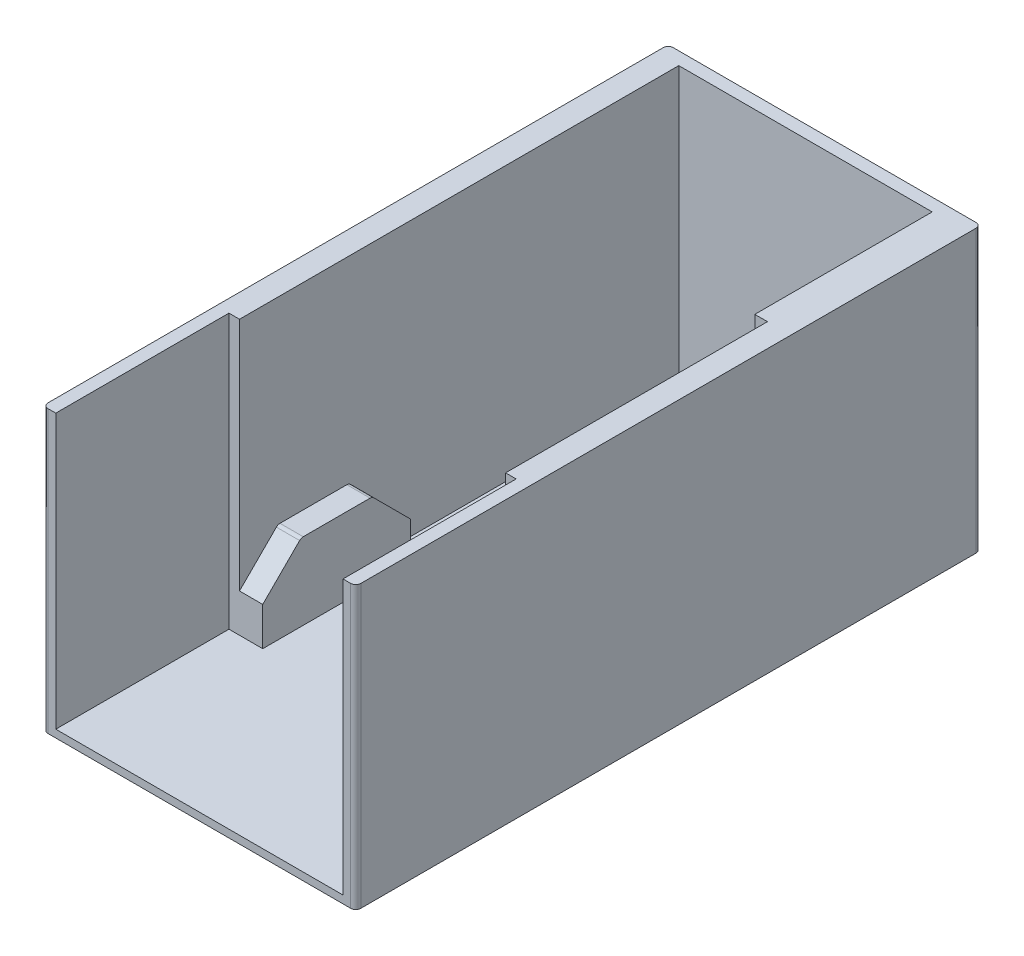
SolidWorks part; units mm, degrees
ref_plane "Front Plane" through (0, 0, 0) normal (0, 0, 1) x (1, 0, 0)
ref_plane "Top Plane" through (0, 0, 0) normal (0, 1, 0) x (1, 0, 0)
ref_plane "Right Plane" through (0, 0, 0) normal (1, 0, 0) x (0, 0, -1)
sketch "Sketch1" plane through (0, 0, 0) normal (0, 1, 0) x (1, 0, 0)
  line L0 (0, 0) -> (0, 2095.5) construction
  line L1 (-863.6, -520.7) -> (863.6, -520.7)
  line L2 (-863.6, -520.7) -> (-863.6, 520.7)
  line L3 (-863.6, 520.7) -> (863.6, 520.7)
  line L4 (863.6, -520.7) -> (863.6, 520.7)
  line L5 (-863.6, -520.7) -> (863.6, 520.7) construction
  line L6 (-863.6, 520.7) -> (863.6, -520.7) construction
  line L7 (-660.4, 520.7) -> (660.4, 520.7)
  line L8 (-660.4, 520.7) -> (-660.4, 1409.7)
  line L9 (-660.4, 1409.7) -> (660.4, 1409.7)
  line L10 (660.4, 520.7) -> (660.4, 1409.7)
  line L12 (-800.1, 1409.7) -> (800.1, 1409.7)
  line L13 (-800.1, 1409.7) -> (-800.1, 2095.5)
  line L14 (-800.1, 2095.5) -> (800.1, 2095.5)
  line L15 (800.1, 1409.7) -> (800.1, 2095.5)
  line L16 (-800.1, 2095.5) -> (723.9, 2095.5)
  line L17 (-800.1, 2095.5) -> (-800.1, 3162.3)
  line L18 (-800.1, 3162.3) -> (723.9, 3162.3)
  line L19 (723.9, 2095.5) -> (723.9, 3162.3)
  point P0 (0, 0)
  point P10 (0, 1409.7)
  point P13 (0, 2095.5)
  dimension "D1" = 1727.2
  dimension "D2" = 1041.4
  dimension "D3" = 1320.8
  dimension "D4" = 889
  dimension "D5" = 1600.2
  dimension "D6" = 685.8
  dimension "D7" = 1524
  dimension "D8" = 1066.8
sketch "Sketch2" plane through (0, 0, 0) normal (0, 1, 0) x (1, 0, 0)
  line L0 (-275, 3062.3) -> (-275, 3012.3) construction
  line L1 (-450, 3012.3) -> (-100, 3012.3)
  line L2 (-450, 3012.3) -> (-450, 2512.3)
  line L3 (-450, 2512.3) -> (-100, 2512.3)
  line L4 (-100, 3012.3) -> (-100, 2512.3)
  line L5 (-500, 3062.3) -> (-50, 3062.3)
  line L6 (-500, 3062.3) -> (-500, 2462.3)
  line L7 (-500, 2462.3) -> (-50, 2462.3)
  line L8 (-50, 3062.3) -> (-50, 2462.3)
  line L9 (-450, 2762.3) -> (-500, 2762.3) construction
  line L10 (100, 3012.3) -> (100, 2512.3)
  line L11 (100, 3012.3) -> (450, 3012.3)
  line L12 (450, 3012.3) -> (450, 2512.3)
  line L13 (100, 2512.3) -> (450, 2512.3)
  line L14 (50, 3062.3) -> (50, 2462.3)
  line L15 (50, 3062.3) -> (500, 3062.3)
  line L16 (500, 3062.3) -> (500, 2462.3)
  line L17 (50, 2462.3) -> (500, 2462.3)
  line L18 (100, 2312.3) -> (100, 1812.3)
  line L19 (100, 2312.3) -> (450, 2312.3)
  line L20 (450, 2312.3) -> (450, 1812.3)
  line L21 (100, 1812.3) -> (450, 1812.3)
  line L22 (50, 2362.3) -> (50, 1762.3)
  line L23 (50, 2362.3) -> (500, 2362.3)
  line L24 (500, 2362.3) -> (500, 1762.3)
  line L25 (50, 1762.3) -> (500, 1762.3)
  line L26 (100, 1612.3) -> (100, 1112.3)
  line L27 (100, 1612.3) -> (450, 1612.3)
  line L28 (450, 1612.3) -> (450, 1112.3)
  line L29 (100, 1112.3) -> (450, 1112.3)
  line L30 (50, 1662.3) -> (50, 1062.3)
  line L31 (50, 1662.3) -> (500, 1662.3)
  line L32 (500, 1662.3) -> (500, 1062.3)
  line L33 (50, 1062.3) -> (500, 1062.3)
  line L34 (100, 912.3) -> (100, 412.3)
  line L35 (100, 912.3) -> (450, 912.3)
  line L36 (450, 912.3) -> (450, 412.3)
  line L37 (100, 412.3) -> (450, 412.3)
  line L38 (50, 962.3) -> (50, 362.3)
  line L39 (50, 962.3) -> (500, 962.3)
  line L40 (500, 962.3) -> (500, 362.3)
  line L41 (50, 362.3) -> (500, 362.3)
  line L42 (-450, 2312.3) -> (-450, 1812.3)
  line L43 (-450, 2312.3) -> (-100, 2312.3)
  line L44 (-100, 2312.3) -> (-100, 1812.3)
  line L45 (-450, 1812.3) -> (-100, 1812.3)
  line L46 (-500, 2362.3) -> (-500, 1762.3)
  line L47 (-500, 2362.3) -> (-50, 2362.3)
  line L48 (-50, 2362.3) -> (-50, 1762.3)
  line L49 (-500, 1762.3) -> (-50, 1762.3)
  line L50 (-450, 1612.3) -> (-450, 1112.3)
  line L51 (-450, 1612.3) -> (-100, 1612.3)
  line L52 (-100, 1612.3) -> (-100, 1112.3)
  line L53 (-450, 1112.3) -> (-100, 1112.3)
  line L54 (-500, 1662.3) -> (-500, 1062.3)
  line L55 (-500, 1662.3) -> (-50, 1662.3)
  line L56 (-50, 1662.3) -> (-50, 1062.3)
  line L57 (-500, 1062.3) -> (-50, 1062.3)
  line L58 (-450, 912.3) -> (-450, 412.3)
  line L59 (-450, 912.3) -> (-100, 912.3)
  line L60 (-100, 912.3) -> (-100, 412.3)
  line L61 (-450, 412.3) -> (-100, 412.3)
  line L62 (-500, 962.3) -> (-500, 362.3)
  line L63 (-500, 962.3) -> (-50, 962.3)
  line L64 (-50, 962.3) -> (-50, 362.3)
  line L65 (-500, 362.3) -> (-50, 362.3)
  line L66 (-450, 3012.3) -> (100, 3012.3) construction
  line L67 (-450, 3012.3) -> (-450, 2312.3) construction
  line L68 (-50, 3062.3) -> (50, 3062.3) construction
  line L69 (0, 3062.3) -> (0, 2095.5) construction
  line L70 (-500, 2462.3) -> (-500, 2362.3)
  line L71 (-550, 3112.3) -> (550, 3112.3)
  line L72 (-550, 3112.3) -> (-550, 312.3)
  line L73 (-550, 312.3) -> (550, 312.3)
  line L74 (550, 3112.3) -> (550, 312.3)
  line L75 (-800.1, 3162.3) -> (723.9, 3162.3) construction
  dimension "D1" = 350
  dimension "D2" = 500
  dimension "D3" = 450
  dimension "D4" = 600
  dimension "D5" = 2
  dimension "D7" = 90
  dimension "D8" = 550
  dimension "D9" = 50
  dimension "D10" = 50
  dimension "D11" = 50
  dimension "D12" = 50
  dimension "D13" = 100
  dimension "D14" = 50
  dimension "D6" = 4
sketch "Resized Everything" plane through (0, 0, 0) normal (0, 1, 0) x (1, 0, 0)
  line L85 (-790.321, 2977.388) -> (-697.865, 2977.388)
  line L86 (-697.865, 2977.388) -> (-697.865, 3039.618)
  line L87 (-790.321, 3039.618) -> (-697.865, 3039.618)
  line L88 (-790.321, 2977.388) -> (-790.321, 3039.618)
  line L89 (-804.545, 2904.49) -> (-683.641, 2904.49)
  line L90 (-683.641, 2904.49) -> (-683.641, 2977.388)
  line L91 (-804.545, 2977.388) -> (-683.641, 2977.388)
  line L92 (-804.545, 2904.49) -> (-804.545, 2977.388)
  line L93 (-800.1, 3039.618) -> (-800.1, 3087.624)
  line L94 (-800.1, 3039.618) -> (-688.086, 3039.618)
  line L95 (-688.086, 3039.618) -> (-688.086, 3087.624)
  line L96 (-800.1, 3087.624) -> (-688.086, 3087.624)
  line L97 (-800.1, 3087.624) -> (-693.42, 3087.624)
  line L98 (-693.42, 3087.624) -> (-693.42, 3162.3)
  line L99 (-800.1, 3162.3) -> (-693.42, 3162.3)
  line L100 (-800.1, 3087.624) -> (-800.1, 3162.3)
  line L101 (-779.093, 3113.3) -> (-779.093, 3106.3)
  line L102 (-779.093, 3113.3) -> (-747.593, 3113.3)
  line L103 (-747.593, 3155.3) -> (-747.593, 3113.3)
  line L104 (-779.093, 3155.3) -> (-747.593, 3155.3)
  line L105 (-779.093, 3155.3) -> (-779.093, 3113.3)
  line L106 (-775.593, 3151.8) -> (-751.093, 3151.8)
  line L107 (-751.093, 3151.8) -> (-751.093, 3116.8)
  line L108 (-775.593, 3116.8) -> (-751.093, 3116.8)
  line L109 (-775.593, 3151.8) -> (-775.593, 3116.8)
  line L110 (-740.593, 3106.3) -> (-740.593, 3064.3)
  line L111 (-740.593, 3064.3) -> (-709.093, 3064.3)
  line L112 (-709.093, 3106.3) -> (-709.093, 3064.3)
  line L113 (-740.593, 3106.3) -> (-709.093, 3106.3)
  line L114 (-737.093, 3102.8) -> (-737.093, 3067.8)
  line L115 (-737.093, 3067.8) -> (-712.593, 3067.8)
  line L116 (-712.593, 3102.8) -> (-712.593, 3067.8)
  line L117 (-737.093, 3102.8) -> (-712.593, 3102.8)
  line L118 (-740.593, 3155.3) -> (-740.593, 3113.3)
  line L119 (-740.593, 3113.3) -> (-709.093, 3113.3)
  line L120 (-709.093, 3155.3) -> (-709.093, 3113.3)
  line L121 (-740.593, 3155.3) -> (-709.093, 3155.3)
  line L122 (-737.093, 3151.8) -> (-737.093, 3116.8)
  line L123 (-737.093, 3151.8) -> (-712.593, 3151.8)
  line L124 (-712.593, 3151.8) -> (-712.593, 3116.8)
  line L125 (-737.093, 3116.8) -> (-712.593, 3116.8)
  line L126 (-740.593, 3008.3) -> (-740.593, 2966.3)
  line L127 (-740.593, 2966.3) -> (-709.093, 2966.3)
  line L128 (-709.093, 3008.3) -> (-709.093, 2966.3)
  line L129 (-740.593, 3008.3) -> (-709.093, 3008.3)
  line L130 (-737.093, 3004.8) -> (-737.093, 2969.8)
  line L131 (-737.093, 2969.8) -> (-712.593, 2969.8)
  line L132 (-712.593, 3004.8) -> (-712.593, 2969.8)
  line L133 (-737.093, 3004.8) -> (-712.593, 3004.8)
  line L134 (-740.593, 3057.3) -> (-740.593, 3015.3)
  line L135 (-740.593, 3015.3) -> (-709.093, 3015.3)
  line L136 (-709.093, 3057.3) -> (-709.093, 3015.3)
  line L137 (-740.593, 3057.3) -> (-709.093, 3057.3)
  line L138 (-737.093, 3053.8) -> (-737.093, 3018.8)
  line L139 (-737.093, 3053.8) -> (-712.593, 3053.8)
  line L140 (-712.593, 3053.8) -> (-712.593, 3018.8)
  line L141 (-737.093, 3018.8) -> (-712.593, 3018.8)
  line L142 (-779.093, 3057.3) -> (-779.093, 3015.3)
  line L143 (-779.093, 3015.3) -> (-747.593, 3015.3)
  line L144 (-747.593, 3057.3) -> (-747.593, 3015.3)
  line L145 (-779.093, 3057.3) -> (-747.593, 3057.3)
  line L146 (-775.593, 3053.8) -> (-775.593, 3018.8)
  line L147 (-775.593, 3018.8) -> (-751.093, 3018.8)
  line L148 (-751.093, 3053.8) -> (-751.093, 3018.8)
  line L149 (-775.593, 3053.8) -> (-751.093, 3053.8)
  line L150 (-779.093, 3106.3) -> (-779.093, 3064.3)
  line L151 (-779.093, 3064.3) -> (-747.593, 3064.3)
  line L152 (-747.593, 3106.3) -> (-747.593, 3064.3)
  line L153 (-779.093, 3106.3) -> (-747.593, 3106.3)
  line L154 (-775.593, 3102.8) -> (-775.593, 3067.8)
  line L155 (-775.593, 3102.8) -> (-751.093, 3102.8)
  line L156 (-751.093, 3102.8) -> (-751.093, 3067.8)
  line L157 (-775.593, 3067.8) -> (-751.093, 3067.8)
  line L158 (-782.593, 3158.8) -> (-705.593, 3158.8)
  line L159 (-705.593, 3158.8) -> (-705.593, 2962.8)
  line L160 (-782.593, 2962.8) -> (-705.593, 2962.8)
  line L161 (-782.593, 3158.8) -> (-782.593, 2962.8)
  line L162 (-779.093, 3008.3) -> (-779.093, 2966.3)
  line L163 (-779.093, 2966.3) -> (-747.593, 2966.3)
  line L164 (-747.593, 3008.3) -> (-747.593, 2966.3)
  line L165 (-779.093, 3008.3) -> (-747.593, 3008.3)
  line L166 (-775.593, 3004.8) -> (-775.593, 2969.8)
  line L167 (-775.593, 3004.8) -> (-751.093, 3004.8)
  line L168 (-751.093, 3004.8) -> (-751.093, 2969.8)
  line L169 (-775.593, 2969.8) -> (-751.093, 2969.8)
sketch "Sketch6" plane through (0, 0, 0) normal (0, 1, 0) x (1, 0, 0)
  line L0 (-800.1, 3162.3) -> (723.9, 3162.3) construction
  line L1 (-748.0935, 2917.905) -> (-748.0935, 3167.3) construction
  line L2 (-809.2275, 2917.905) -> (-686.9595, 2917.905)
  line L3 (-686.9595, 2917.905) -> (-686.9595, 3167.3)
  line L4 (-686.9595, 3167.3) -> (-809.2275, 3167.3)
  line L5 (-696.087, 3048.381) -> (-696.087, 2990.596)
  line L6 (-800.1, 3048.381) -> (-800.1, 2990.596)
  line L7 (-809.2275, 2917.905) -> (-809.2275, 3167.3)
  line L8 (-701.04, 3162.3) -> (-696.087, 3162.3)
  line L9 (-696.087, 3162.3) -> (-696.087, 3092.958)
  line L10 (-804.2275, 2922.905) -> (-809.2275, 2922.905)
  line L11 (-691.9595, 2922.905) -> (-686.9595, 2922.905)
  line L16 (-791.0195, 2990.596) -> (-705.1675, 2990.596)
  line L17 (-705.1675, 2990.596) -> (-705.1675, 3048.381)
  line L18 (-791.0195, 3048.381) -> (-705.1675, 3048.381)
  line L19 (-791.0195, 2990.596) -> (-791.0195, 3048.381)
  line L20 (-804.2275, 2922.905) -> (-691.9595, 2922.905)
  line L21 (-691.9595, 2922.905) -> (-691.9595, 2990.596)
  line L22 (-804.2275, 2990.596) -> (-691.9595, 2990.596)
  line L23 (-804.2275, 2922.905) -> (-804.2275, 2990.596)
  line L24 (-800.1, 3048.381) -> (-800.1, 3092.958)
  line L25 (-800.1, 3048.381) -> (-696.087, 3048.381)
  line L26 (-696.087, 3048.381) -> (-696.087, 3092.958)
  line L27 (-800.1, 3092.958) -> (-696.087, 3092.958)
  line L28 (-800.1, 3092.958) -> (-701.04, 3092.958)
  line L29 (-701.04, 3092.958) -> (-701.04, 3162.3)
  line L30 (-800.1, 3162.3) -> (-701.04, 3162.3)
  line L31 (-800.1, 3092.958) -> (-800.1, 3162.3)
  point P3 (-748.0935, 2922.905)
  dimension "D1" = 239.395
  dimension "D2" = 5
  dimension "D3" = 5
  dimension "D4" = 5
extrude "Boss-Extrude1" add sketch "Sketch6" along normal blind 107 contours L2 L1 L20 L23 L22 L6 L24 L31 L30 L4 L7 | L1 L2 L3 L4 L30 L29 L27 L26 L5 L22 L21 L20 | L29 L27 L9 L8 region at (-801.3852, 0, -3070.3406) region at (-694.8018, 0, -3070.3406) region at (-698.5635, 0, -3127.629)
sketch "Sketch7" plane through (0, 0, 0) normal (0, -1, 0) x (1, 0, 0)
  line L0 (-800.1, -3048.381) -> (-800.1, -2990.596) construction
  line L1 (-696.087, -3048.381) -> (-696.087, -2990.596) construction
  line L2 (-800.1, -3048.381) -> (-800.1, -3092.958) construction
  line L3 (-800.1, -3092.958) -> (-696.087, -3092.958) construction
  line L4 (-800.1, -3092.958) -> (-701.04, -3092.958) construction
  line L5 (-701.04, -3092.958) -> (-701.04, -3162.3) construction
  line L6 (-800.1, -3162.3) -> (-701.04, -3162.3) construction
  line L7 (-800.1, -3092.958) -> (-800.1, -3162.3) construction
  line L8 (-701.04, -3162.3) -> (-696.087, -3162.3) construction
  line L9 (-696.087, -3162.3) -> (-696.087, -3092.958) construction
  line L10 (-696.087, -3048.381) -> (-696.087, -3092.958) construction
  line L11 (-800.1, -3048.381) -> (-696.087, -3048.381) construction
  line L12 (-809.2275, -2917.905) -> (-686.9595, -2917.905) construction
  line L13 (-686.9595, -2917.905) -> (-686.9595, -3167.3) construction
  line L14 (-686.9595, -3167.3) -> (-809.2275, -3167.3) construction
  line L15 (-809.2275, -2917.905) -> (-809.2275, -3167.3) construction
  line L16 (-804.2275, -2922.905) -> (-691.9595, -2922.905) construction
  line L17 (-691.9595, -2922.905) -> (-691.9595, -2990.596) construction
  line L18 (-804.2275, -2990.596) -> (-691.9595, -2990.596) construction
  line L19 (-804.2275, -2922.905) -> (-804.2275, -2990.596) construction
  line L20 (-705.1675, -2990.596) -> (-705.1675, -3048.381) construction
  line L21 (-791.0195, -3048.381) -> (-705.1675, -3048.381) construction
  line L22 (-791.0195, -2990.596) -> (-791.0195, -3048.381) construction
  line L23 (-791.0195, -2990.596) -> (-705.1675, -2990.596) construction
  line L24 (-800.1, -3048.381) -> (-800.1, -2990.596)
  line L25 (-696.087, -3048.381) -> (-696.087, -2990.596)
  line L26 (-800.1, -3048.381) -> (-800.1, -3092.958)
  line L27 (-800.1, -3092.958) -> (-696.087, -3092.958)
  line L28 (-800.1, -3092.958) -> (-701.04, -3092.958)
  line L29 (-701.04, -3092.958) -> (-701.04, -3162.3)
  line L30 (-800.1, -3162.3) -> (-701.04, -3162.3)
  line L31 (-800.1, -3092.958) -> (-800.1, -3162.3)
  line L32 (-701.04, -3162.3) -> (-696.087, -3162.3)
  line L33 (-696.087, -3162.3) -> (-696.087, -3092.958)
  line L34 (-696.087, -3048.381) -> (-696.087, -3092.958)
  line L35 (-800.1, -3048.381) -> (-696.087, -3048.381)
  line L36 (-809.2275, -2917.905) -> (-686.9595, -2917.905)
  line L37 (-686.9595, -2917.905) -> (-686.9595, -3167.3)
  line L38 (-686.9595, -3167.3) -> (-809.2275, -3167.3)
  line L39 (-809.2275, -2917.905) -> (-809.2275, -3167.3)
  line L40 (-804.2275, -2922.905) -> (-691.9595, -2922.905)
  line L41 (-691.9595, -2922.905) -> (-691.9595, -2990.596)
  line L42 (-804.2275, -2990.596) -> (-691.9595, -2990.596)
  line L43 (-804.2275, -2922.905) -> (-804.2275, -2990.596)
  line L44 (-705.1675, -2990.596) -> (-705.1675, -3048.381)
  line L45 (-791.0195, -3048.381) -> (-705.1675, -3048.381)
  line L46 (-791.0195, -2990.596) -> (-791.0195, -3048.381)
  line L47 (-791.0195, -2990.596) -> (-705.1675, -2990.596)
extrude "Boss-Extrude2" add sketch "Sketch7" along normal blind 3 contours L39 L38 L37 L36
sketch "Sketch8" plane through (0, 0, 0) normal (0, 1, 0) x (1, 0, 0)
  line L0 (-691.9595, 2922.905) -> (-686.9595, 2922.905) construction
  line L1 (-804.2275, 2922.905) -> (-809.2275, 2922.905) construction
  line L2 (-800.1, 3048.381) -> (-800.1, 2990.596) construction
  line L3 (-696.087, 3048.381) -> (-696.087, 2990.596) construction
  line L4 (-800.1, 3048.381) -> (-800.1, 3092.958) construction
  line L5 (-800.1, 3092.958) -> (-696.087, 3092.958) construction
  line L6 (-800.1, 3092.958) -> (-701.04, 3092.958) construction
  line L7 (-701.04, 3092.958) -> (-701.04, 3162.3) construction
  line L8 (-800.1, 3162.3) -> (-701.04, 3162.3) construction
  line L9 (-800.1, 3092.958) -> (-800.1, 3162.3) construction
  line L10 (-804.2275, 2922.905) -> (-691.9595, 2922.905) construction
  line L11 (-691.9595, 2922.905) -> (-691.9595, 2990.596) construction
  line L12 (-804.2275, 2990.596) -> (-691.9595, 2990.596) construction
  line L13 (-804.2275, 2922.905) -> (-804.2275, 2990.596) construction
  line L14 (-701.04, 3162.3) -> (-696.087, 3162.3) construction
  line L15 (-696.087, 3162.3) -> (-696.087, 3092.958) construction
  line L16 (-696.087, 3048.381) -> (-696.087, 3092.958) construction
  line L17 (-800.1, 3048.381) -> (-696.087, 3048.381) construction
  line L18 (-809.2275, 2917.905) -> (-686.9595, 2917.905) construction
  line L19 (-686.9595, 2917.905) -> (-686.9595, 3167.3) construction
  line L20 (-686.9595, 3167.3) -> (-809.2275, 3167.3) construction
  line L21 (-809.2275, 2917.905) -> (-809.2275, 3167.3) construction
  line L22 (-705.1675, 2990.596) -> (-705.1675, 3048.381) construction
  line L23 (-791.0195, 3048.381) -> (-705.1675, 3048.381) construction
  line L24 (-791.0195, 2990.596) -> (-791.0195, 3048.381) construction
  line L25 (-791.0195, 2990.596) -> (-705.1675, 2990.596) construction
  line L26 (-691.9595, 2922.905) -> (-686.9595, 2922.905)
  line L27 (-804.2275, 2922.905) -> (-809.2275, 2922.905)
  line L28 (-800.1, 3048.381) -> (-800.1, 2990.596)
  line L29 (-696.087, 3048.381) -> (-696.087, 2990.596)
  line L30 (-800.1, 3048.381) -> (-800.1, 3092.958)
  line L31 (-800.1, 3092.958) -> (-696.087, 3092.958)
  line L32 (-800.1, 3092.958) -> (-701.04, 3092.958)
  line L33 (-701.04, 3092.958) -> (-701.04, 3162.3)
  line L34 (-800.1, 3162.3) -> (-701.04, 3162.3)
  line L35 (-800.1, 3092.958) -> (-800.1, 3162.3)
  line L36 (-804.2275, 2922.905) -> (-691.9595, 2922.905)
  line L37 (-691.9595, 2922.905) -> (-691.9595, 2990.596)
  line L38 (-804.2275, 2990.596) -> (-691.9595, 2990.596)
  line L39 (-804.2275, 2922.905) -> (-804.2275, 2990.596)
  line L40 (-701.04, 3162.3) -> (-696.087, 3162.3)
  line L41 (-696.087, 3162.3) -> (-696.087, 3092.958)
  line L42 (-696.087, 3048.381) -> (-696.087, 3092.958)
  line L43 (-800.1, 3048.381) -> (-696.087, 3048.381)
  line L44 (-809.2275, 2917.905) -> (-686.9595, 2917.905)
  line L45 (-686.9595, 2917.905) -> (-686.9595, 3167.3)
  line L46 (-686.9595, 3167.3) -> (-809.2275, 3167.3)
  line L47 (-809.2275, 2917.905) -> (-809.2275, 3167.3)
  line L48 (-705.1675, 2990.596) -> (-705.1675, 3048.381)
  line L49 (-791.0195, 3048.381) -> (-705.1675, 3048.381)
  line L50 (-791.0195, 2990.596) -> (-791.0195, 3048.381)
  line L51 (-791.0195, 2990.596) -> (-705.1675, 2990.596)
  line M17 (-696.087, 2990.596) -> (-696.087, 3092.958)
  line M21 (-800.1, 3162.3) -> (-800.1, 2990.596)
extrude "Boss-Extrude3" add sketch "Sketch8" along normal blind 30 contours L38 L50 L43 M21 | L48 L38 L43 M17 region at (-700.6273, 0, -3019.4885) region at (-795.5597, 0, -3019.4885)
ref_plane "Plane1" through (-748.0935, 0, 0) normal (1, 0, 0) x (0, 0, -1)
sketch "Sketch9" plane through (-791.0195, 0, 0) normal (1, 0, 0) x (0, 0, -1)
  line L0 (2990.596, 15) -> (3005.596, 30)
  line L1 (3019.4885, 30) -> (3019.4885, 0) construction
  line L2 (3048.381, 15) -> (3033.381, 30)
  line L4 (2990.596, 0) -> (3048.381, 0)
  line L5 (3048.381, 0) -> (3048.381, 30)
  line L6 (3048.381, 30) -> (2990.596, 30)
  line L7 (2990.596, 30) -> (2990.596, 0)
  line L8 (2990.596, 0) -> (3048.381, 0)
  line L9 (3048.381, 0) -> (3048.381, 30)
  line L10 (3048.381, 30) -> (2990.596, 30)
  line L11 (2990.596, 30) -> (2990.596, 0)
  line M8 (3048.381, 0) -> (3048.381, 30)
  line M9 (3048.381, 30) -> (2990.596, 30)
  line M10 (2990.596, 30) -> (2990.596, 0)
  dimension "D2" = 45
  dimension "D1" = 0
extrude "Cut-Extrude1" cut sketch "Sketch9" against normal up to surface (9.0805 mm away) contours L0 M10 M9 | L2 M8 M9 region at (-791.0195, 25, -2995.596) region at (-791.0195, 25, -3043.381) up to face at (-800.1, 45.6667, -3067.0923)
sketch "Sketch10" plane through (-705.1675, 0, 0) normal (-1, 0, 0) x (0, 0, 1)
  line L0 (-3048.381, 15) -> (-3033.381, 30) construction
  line L1 (-2990.596, 15) -> (-3005.596, 30) construction
  line L2 (-3048.381, 15) -> (-3033.381, 30)
  line L3 (-2990.596, 15) -> (-3005.596, 30)
  line L4 (-3048.381, 0) -> (-2990.596, 0)
  line L5 (-3048.381, 30) -> (-3048.381, 0)
  line L6 (-2990.596, 30) -> (-3048.381, 30)
  line L7 (-2990.596, 0) -> (-2990.596, 30)
  line L8 (-3048.381, 0) -> (-2990.596, 0)
  line L9 (-3048.381, 30) -> (-3048.381, 0)
  line L10 (-2990.596, 30) -> (-3048.381, 30)
  line L11 (-2990.596, 0) -> (-2990.596, 30)
  line M6 (-2990.596, 0) -> (-2990.596, 30)
  line M7 (-2990.596, 30) -> (-3048.381, 30)
  line M8 (-3048.381, 30) -> (-3048.381, 0)
  dimension "D1" = 0
extrude "Cut-Extrude2" cut sketch "Sketch10" against normal up to surface (9.0805 mm away) contours L2 M8 M7 | L3 M6 M7 region at (-705.1675, 25, -3043.381) region at (-705.1675, 25, -2995.596) up to face at (-696.087, 45.6667, -3043.9783)
fillet "Fillet1" radius 2 8 edges at (-686.9595, 53.5, -2922.905) (-686.9595, 52, -3167.3) (-809.2275, 52, -3167.3) (-809.2275, 53.5, -2922.905) (-700.6272, 30, -3033.381) (-700.6272, 30, -3005.596) (-795.5598, 30, -3033.381) (-795.5598, 30, -3005.596) tangent propagation no
sketch "Sketch11" plane through (0, 0, 0) normal (0, 1, 0) x (-1, 0, 0)
  line L0 (804.2275, -2922.905) -> (691.9595, -2922.905)
  line L18 (791.0195, -3048.381) -> (791.0195, -2990.596)
  line L19 (791.0195, -2990.596) -> (804.2275, -2990.596)
  line L20 (804.2275, -2990.596) -> (804.2275, -2922.905)
  line L21 (804.2275, -2922.905) -> (807.2275, -2922.905)
  line L22 (809.2275, -2924.905) -> (809.2275, -2917.905)
  line L23 (809.2275, -2917.905) -> (686.9595, -2917.905)
  line L24 (686.9595, -2917.905) -> (686.9595, -2924.905)
  line L25 (688.9595, -2922.905) -> (691.9595, -2922.905)
  line L26 (691.9595, -2922.905) -> (691.9595, -2990.596)
  line L27 (691.9595, -2990.596) -> (705.1675, -2990.596)
  line L28 (705.1675, -2990.596) -> (705.1675, -3048.381)
  line L29 (705.1675, -3048.381) -> (696.087, -3048.381)
  line L30 (696.087, -3048.381) -> (696.087, -3092.958)
  line L31 (696.087, -3092.958) -> (701.04, -3092.958)
  line L32 (701.04, -3092.958) -> (701.04, -3162.3)
  line L33 (701.04, -3162.3) -> (800.1, -3162.3)
  line L34 (800.1, -3162.3) -> (800.1, -3048.381)
  line L35 (800.1, -3048.381) -> (791.0195, -3048.381)
  line L36 (791.0195, -3048.381) -> (791.0195, -2990.596)
  line L37 (791.0195, -2990.596) -> (804.2275, -2990.596)
  line L38 (804.2275, -2990.596) -> (804.2275, -2922.905)
  line L39 (804.2275, -2922.905) -> (807.2275, -2922.905)
  line L40 (809.2275, -2924.905) -> (809.2275, -2917.905)
  line L41 (809.2275, -2917.905) -> (686.9595, -2917.905)
  line L42 (686.9595, -2917.905) -> (686.9595, -2924.905)
  line L43 (688.9595, -2922.905) -> (691.9595, -2922.905)
  line L44 (691.9595, -2922.905) -> (691.9595, -2990.596)
  line L45 (691.9595, -2990.596) -> (705.1675, -2990.596)
  line L46 (705.1675, -2990.596) -> (705.1675, -3048.381)
  line L47 (705.1675, -3048.381) -> (696.087, -3048.381)
  line L48 (696.087, -3048.381) -> (696.087, -3092.958)
  line L49 (696.087, -3092.958) -> (701.04, -3092.958)
  line L50 (701.04, -3092.958) -> (701.04, -3162.3)
  line L51 (701.04, -3162.3) -> (800.1, -3162.3)
  line L52 (800.1, -3162.3) -> (800.1, -3048.381)
  line L53 (800.1, -3048.381) -> (791.0195, -3048.381)
  arc A2 (809.2275, -2924.905) -> (807.2275, -2922.905) centre (807.2275, -2924.905) ccw
  arc A3 (688.9595, -2922.905) -> (686.9595, -2924.905) centre (688.9595, -2924.905) ccw
  arc A4 (809.2275, -2924.905) -> (807.2275, -2922.905) centre (807.2275, -2924.905) ccw
  arc A5 (688.9595, -2922.905) -> (686.9595, -2924.905) centre (688.9595, -2924.905) ccw
  line M24 (804.2275, -2922.905) -> (807.2275, -2922.905)
  arc M25 (807.2275, -2922.905) -> (809.2275, -2924.905) centre (807.2275, -2924.905) cw
  line M26 (809.2275, -2924.905) -> (809.2275, -2917.905)
  line M27 (809.2275, -2917.905) -> (686.9595, -2917.905)
  line M28 (686.9595, -2917.905) -> (686.9595, -2924.905)
  arc M29 (686.9595, -2924.905) -> (688.9595, -2922.905) centre (688.9595, -2924.905) cw
  line M30 (688.9595, -2922.905) -> (691.9595, -2922.905)
  dimension "D1" = 0
extrude "Cut-Extrude3" cut sketch "Sketch11" against normal through all contours L0 M24 M25 M26 M27 M28 M29 M30 region at (-748.0935, 0, -2920.4133)
equation "\"alpha\"= 1"
equation "\"bin_width\"= 0.5"
equation "\"bin_depth\"= 0.35"
equation "\"bin_height\"= 0.35"
